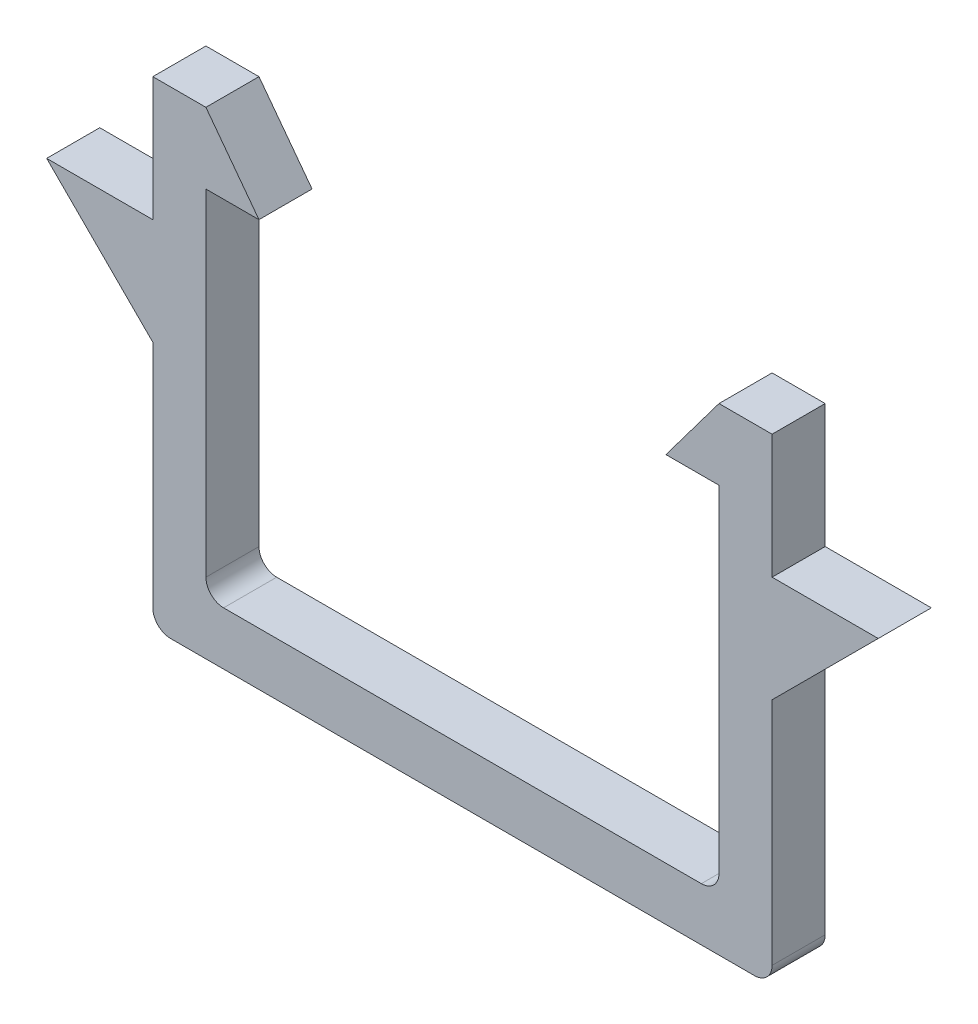
SolidWorks part; units mm, degrees
material "Custom PLA"
ref_plane "Front Plane" through (0, 0, 0) normal (0, 0, 1) x (1, 0, 0)
ref_plane "Top Plane" through (0, 0, 0) normal (0, 1, 0) x (1, 0, 0)
ref_plane "Right Plane" through (0, 0, 0) normal (1, 0, 0) x (0, 0, -1)
sketch "Sketch1" plane through (0, 0, 0) normal (0, 0, 1) x (1, 0, 0)
  line L0 (-13.5, 3) -> (13.5, 3)
  line L1 (-14.5, 23) -> (-14.5, 4)
  line L2 (14.5, 4) -> (14.5, 23)
  line L3 (17.5, 1) -> (17.5, 14)
  line L4 (-17.5, 1) -> (-17.5, 14)
  line L5 (-16.5, 0) -> (16.5, 0)
  line L6 (-14.5, 23) -> (-11.5, 23)
  line L9 (14.5, 23) -> (11.5, 23)
  line L12 (17.5, 27) -> (14.5, 27)
  line L13 (-17.5, 27) -> (-14.5, 27)
  line L14 (-14.5, 27) -> (-11.5, 23)
  line L15 (11.5, 23) -> (14.5, 27)
  line L16 (-23.5, 20) -> (-17.5, 14)
  line L17 (-17.5, 20) -> (-23.5, 20)
  line L18 (-17.5, 20) -> (-17.5, 27)
  line L19 (0, -55) -> (0, 55) construction
  line L20 (17.5, 20) -> (23.5, 20)
  line L21 (23.5, 20) -> (17.5, 14)
  line L22 (17.5, 20) -> (17.5, 27)
  arc A0 (17.5, 1) -> (16.5, 0) centre (16.5, 1) cw
  arc A1 (14.5, 4) -> (13.5, 3) centre (13.5, 4) cw
  arc A2 (-16.5, 0) -> (-17.5, 1) centre (-16.5, 1) cw
  arc A3 (-13.5, 3) -> (-14.5, 4) centre (-13.5, 4) cw
  point P14 (17.5, 0)
  point P17 (14.5, 3)
  point P20 (-17.5, 0)
  point P23 (-14.5, 3)
  dimension "D12" = 1
  dimension "D2" = 29
  dimension "D3" = 3
  dimension "D4" = 3
  dimension "D5" = 3
  dimension "D6" = 3
  dimension "D7" = 20
  dimension "D8" = 26
  dimension "D9" = 20
  dimension "D10" = 26
  dimension "D11" = 3
  dimension "D13" = 3
  dimension "D14" = 3
  dimension "D15" = 3
  dimension "D16" = 6
  dimension "D17" = 8.4853
extrude "Boss-Extrude1" add sketch "Sketch1" along normal mid plane 3
